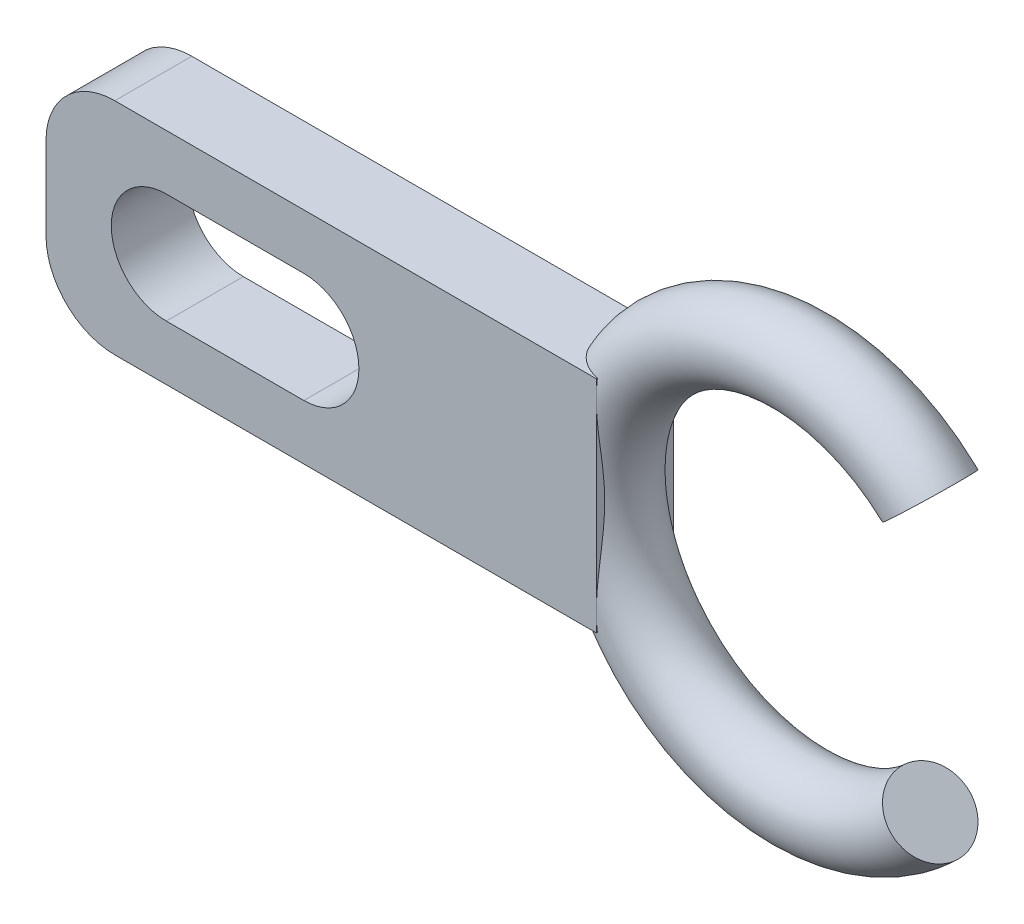
SolidWorks part; units mm, degrees
ref_plane "Plano frontal" through (0, 0, 0) normal (0, 0, 1) x (1, 0, 0)
ref_plane "Plano superior" through (0, 0, 0) normal (0, 1, 0) x (1, 0, 0)
ref_plane "Plano direito" through (0, 0, 0) normal (1, 0, 0) x (0, 0, -1)
sketch "Esboço2" plane through (0, 0, 0) normal (0, 1, 0) x (1, 0, 0)
  line L0 (0, 0) -> (0, 8.2994) construction
  circle A0 centre (13.75, 0) radius 2.8
  dimension "D1" = 13.75
revolve "Revolução1" add sketch "Esboço2" angle 360 about L0
sketch "Esboço3" plane through (0, 0, 0) normal (0, 0, 1) x (1, 0, 0)
  line L0 (-1.2027, 0) -> (18.0412, 17.941)
  line L1 (3.08, 0) -> (-3.08, 0) construction
  line L2 (-6.1474, 0) -> (26.9282, 0) construction
  line L3 (-1.2027, 0) -> (18.0412, -17.941)
  line L4 (18.0412, 17.941) -> (18.0412, -17.941)
extrude "Corte-extrusão1" cut sketch "Esboço3" against normal blind 10 and the other way blind 10
sketch "Esboço5" plane through (0, 0, 0) normal (1, 0, 0) x (0, 0, -1)
  line L0 (2.8, -13.75) -> (2.8, 13.75) construction
  line L1 (-2.8, -8) -> (2.8, -8)
  line L2 (-2.8, -8) -> (-2.8, 8)
  line L3 (-2.8, 8) -> (2.8, 8)
  line L4 (2.8, -8) -> (2.8, 8)
  line L5 (-2.8, -8) -> (2.8, 8) construction
  line L6 (-2.8, 8) -> (2.8, -8) construction
  point P0 (0, 0)
extrude "Ressalto-extrusão1" add sketch "Esboço5" against normal blind 40 from offset 12 offset against normal yes
fillet "Filete1" radius 5 2 edges at (-52, 8, 0) (-52, -8, 0)
sketch "Esboço7" plane through (0, 0, -2.8) normal (0, 0, -1) x (-1, 0, 0)
  line L0 (3.2447, 0) -> (-3.2447, 0) construction
  line L1 (33.2543, 4) -> (43.2543, 4)
  line L2 (43.2543, -4) -> (33.2543, -4)
  arc A0 (43.2543, -4) -> (43.2543, 4) centre (43.2543, 0) ccw
  arc A1 (33.2543, 4) -> (33.2543, -4) centre (33.2543, 0) ccw
  dimension "D1" = 10
  dimension "D2" = 8
extrude "Corte-extrusão2" cut sketch "Esboço7" against normal blind 19
